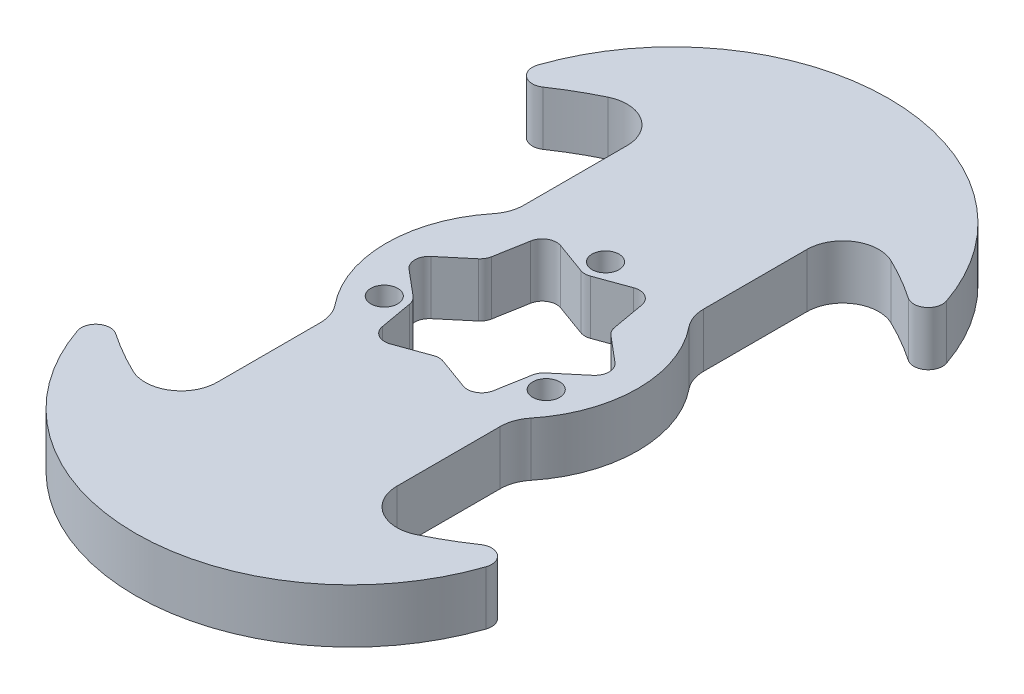
SolidWorks part; units mm, degrees
material "AISI 4340 Steel, annealed"
ref_plane "Front Plane" through (0, 0, 0) normal (0, 0, 1) x (1, 0, 0)
ref_plane "Top Plane" through (0, 0, 0) normal (0, 1, 0) x (1, 0, 0)
ref_plane "Right Plane" through (0, 0, 0) normal (1, 0, 0) x (0, 0, -1)
sketch "Sketch1" plane through (0, 0, 0) normal (0, 1, 0) x (1, 0, 0)
  line L0 (0, 0) -> (-15.875, 0) construction
  line L2 (-15.875, 36.1952) -> (-15.875, 17.9605)
  line L4 (15.875, 36.1952) -> (15.875, 17.9605)
  line L5 (-15.875, 50.8) -> (15.875, -50.8) construction
  line L6 (-15.875, -50.8) -> (15.875, 50.8) construction
  line L7 (6.4359, 15.0359) -> (0.8729, 13.0168)
  line L8 (-0.8603, 13.0122) -> (-6.4359, 15.0359)
  line L9 (-9.8035, 13.0916) -> (-10.8376, 7.2577)
  line L10 (-11.7042, 5.7568) -> (-16.2394, 1.9443)
  line L11 (-16.2394, -1.9443) -> (-11.7042, -5.7568)
  line L12 (-10.8376, -7.2577) -> (-9.8035, -13.0916)
  line L13 (-6.4359, -15.0359) -> (-0.8597, -13.012)
  line L14 (0.8724, -13.0166) -> (6.4359, -15.0359)
  line L15 (9.8035, -13.0916) -> (10.8376, -7.2577)
  line L16 (11.7042, -5.7568) -> (16.2394, -1.9443)
  line L17 (16.2394, 1.9443) -> (11.7042, 5.7568)
  line L18 (10.8376, 7.2577) -> (9.8035, 13.0916)
  line L19 (0.0067, 12.8621) -> (0.0067, -12.8621) construction
  line L20 (-17.145, 0) -> (12.065, 0) construction
  line L21 (15.875, -17.9605) -> (15.875, -36.1952)
  line L22 (-15.875, -17.9605) -> (-15.875, -36.1952)
  arc A1 (32.2482, 37.7166) -> (24.9925, 41.9104) centre (0, -9.7025) ccw
  arc A2 (36.082, 40.6326) -> (-36.082, 40.6326) centre (0, 28.3975) ccw
  arc A3 (36.082, -40.6326) -> (-36.082, -40.6326) centre (0, -28.3975) cw
  arc A4 (32.2482, -37.7166) -> (24.9925, -41.9104) centre (0, 9.7025) cw
  arc A5 (-24.9925, 41.9104) -> (-32.2482, 37.7166) centre (0, -9.7025) ccw
  arc A6 (-24.9925, -41.9104) -> (-32.2482, -37.7166) centre (0, 9.7025) cw
  arc A7 (-15.875, 36.1952) -> (-24.9925, 41.9104) centre (-22.225, 36.1952) ccw
  arc A8 (15.875, 36.1952) -> (24.9925, 41.9104) centre (22.225, 36.1952) cw
  arc A9 (-24.9925, -41.9104) -> (-15.875, -36.1952) centre (-22.225, -36.1952) ccw
  arc A10 (24.9925, -41.9104) -> (15.875, -36.1952) centre (22.225, -36.1952) cw
  circle A11 centre (-14.2981, -8.255) radius 2.3813
  circle A12 centre (0, 16.51) radius 2.3813
  circle A13 centre (14.2981, -8.255) radius 2.3813
  arc A14 (9.8035, 13.0916) -> (6.4359, 15.0359) centre (7.3025, 12.6483) ccw
  arc A15 (-0.8603, 13.0122) -> (0.8729, 13.0168) centre (0, 15.4021) ccw
  arc A16 (-6.4359, 15.0359) -> (-9.8035, 13.0916) centre (-7.3025, 12.6483) ccw
  arc A17 (-11.7042, 5.7568) -> (-10.8376, 7.2577) centre (-13.3386, 7.7011) ccw
  arc A18 (-16.2394, 1.9443) -> (-16.2394, -1.9443) centre (-14.605, 0) ccw
  arc A19 (-10.8376, -7.2577) -> (-11.7042, -5.7568) centre (-13.3386, -7.7011) ccw
  arc A20 (-9.8035, -13.0916) -> (-6.4359, -15.0359) centre (-7.3025, -12.6483) ccw
  arc A21 (0.8724, -13.0166) -> (-0.8597, -13.012) centre (0, -15.4021) ccw
  arc A22 (6.4359, -15.0359) -> (9.8035, -13.0916) centre (7.3025, -12.6483) ccw
  arc A23 (11.7042, -5.7568) -> (10.8376, -7.2577) centre (13.3386, -7.7011) ccw
  arc A24 (16.2394, -1.9443) -> (16.2394, 1.9443) centre (14.605, 0) ccw
  arc A25 (10.8376, 7.2577) -> (11.7042, 5.7568) centre (13.3386, 7.7011) ccw
  arc A26 (-17.2861, 13.9693) -> (-17.2861, -13.9693) centre (0, 0) ccw
  arc A27 (17.2861, -13.9693) -> (17.2861, 13.9693) centre (0, 0) ccw
  arc A28 (-17.2861, 13.9693) -> (-15.875, 17.9605) centre (-22.225, 17.9605) ccw
  arc A29 (-15.875, -17.9605) -> (-17.2861, -13.9693) centre (-22.225, -17.9605) ccw
  arc A30 (15.875, -17.9605) -> (17.2861, -13.9693) centre (22.225, -17.9605) cw
  arc A31 (15.875, 17.9605) -> (17.2861, 13.9693) centre (22.225, 17.9605) ccw
  arc A32 (-32.2482, 37.7166) -> (-36.082, 40.6326) centre (-33.6765, 39.817) cw
  arc A33 (36.082, 40.6326) -> (32.2482, 37.7166) centre (33.6765, 39.817) cw
  arc A34 (-36.082, -40.6326) -> (-32.2482, -37.7166) centre (-33.6765, -39.817) cw
  arc A35 (36.082, -40.6326) -> (32.2482, -37.7166) centre (33.6765, -39.817) ccw
  point P0 (0, 0)
  point P22 (-15.875, 45.402)
  point P27 (-15.875, -45.402)
  point P86 (15.875, -15.5543)
  point P91 (-37.763, 33.4539)
  point P94 (37.763, 33.4539)
  point P97 (-37.763, -33.4539)
  point P100 (37.763, -33.4539)
  point P146 (0, 0)
  dimension "D3" = 6.35
  dimension "D4" = 6.35
  dimension "D5" = 6.35
  dimension "D6" = 6.35
  dimension "D7" = 44.45
  dimension "D8" = 6.35
  dimension "D9" = 6.35
  dimension "D10" = 6.35
  dimension "D11" = 6.35
  dimension "D12" = 2.54
  dimension "D13" = 2.54
  dimension "D14" = 2.54
  dimension "D15" = 2.54
  dimension "D1" = 101.6
  dimension "D2" = 31.75
extrude "Boss-Extrude1" add sketch "Sketch1" along normal blind 9.525
